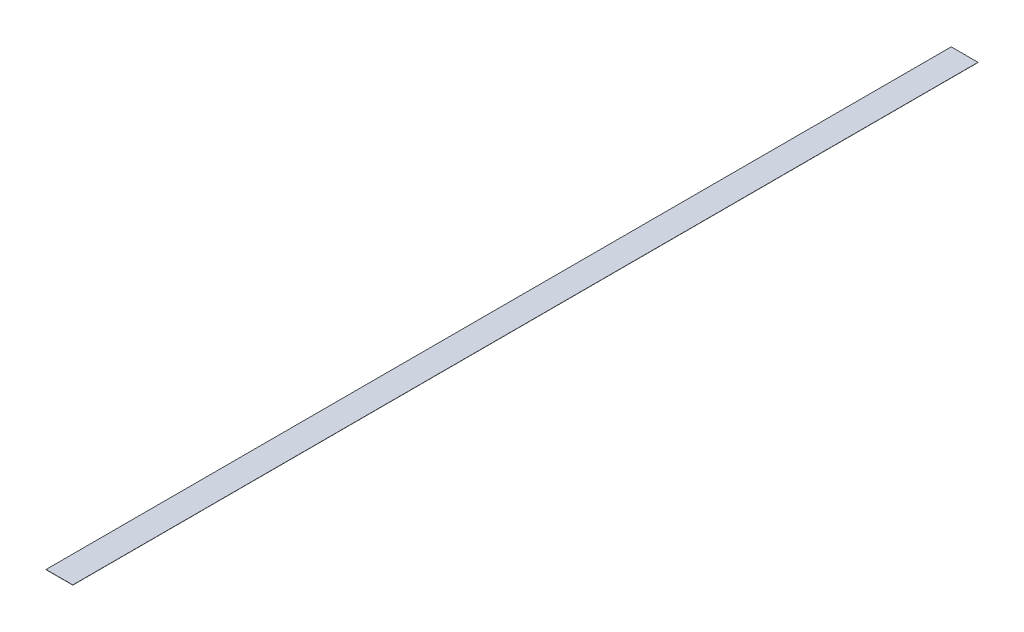
SolidWorks part; units mm, degrees
ref_plane "Front Plane" through (0, 0, 0) normal (0, 0, 1) x (1, 0, 0)
ref_plane "Top Plane" through (0, 0, 0) normal (0, 1, 0) x (1, 0, 0)
ref_plane "Right Plane" through (0, 0, 0) normal (1, 0, 0) x (0, 0, -1)
sketch "Sketch1" plane through (0, 0, 0) normal (0, 1, 0) x (1, 0, 0)
  line L5 (0, 0) -> (15, 0)
  line L6 (0, 0) -> (0, -507)
  line L7 (0, -507) -> (15, -507)
  line L8 (15, 0) -> (15, -507)
  dimension "D1" = 507
  dimension "D2" = 15
extrude "Boss-Extrude1" add sketch "Sketch1" along normal blind 0.1 contours L6 L7 L8 L5
sketch "Sketch2" plane through (0, 0.1, 0) normal (0, 1, 0) x (1, 0, 0)
  line L0 (0, -487) -> (15, -483.537) construction
  line L1 (0, 0) -> (0, -507) construction
  line L2 (15, 0) -> (15, -507) construction
  line L3 (5.0641, -485.8309) -> (5.0641, -457.2309) construction
  circle A0 centre (5.0641, -485.8309) radius 1
  circle A1 centre (9.9359, -484.7061) radius 1
  circle A2 centre (5.0641, -457.2309) radius 1
  circle A3 centre (9.9359, -456.1061) radius 1
  circle A4 centre (5.0641, -428.6309) radius 1
  circle A5 centre (9.9359, -427.5061) radius 1
  circle A6 centre (5.0641, -400.0309) radius 1
  circle A7 centre (9.9359, -398.9061) radius 1
  circle A8 centre (5.0641, -371.4309) radius 1
  circle A9 centre (9.9359, -370.3061) radius 1
  circle A10 centre (5.0641, -342.8309) radius 1
  circle A11 centre (9.9359, -341.7061) radius 1
  circle A12 centre (5.0641, -314.2309) radius 1
  circle A13 centre (9.9359, -313.1061) radius 1
  circle A14 centre (5.0641, -285.6309) radius 1
  circle A15 centre (9.9359, -284.5061) radius 1
  circle A16 centre (5.0641, -257.0309) radius 1
  circle A17 centre (9.9359, -255.9061) radius 1
  circle A18 centre (5.0641, -228.4309) radius 1
  circle A19 centre (9.9359, -227.3061) radius 1
  circle A20 centre (5.0641, -199.8309) radius 1
  circle A21 centre (9.9359, -198.7061) radius 1
  circle A22 centre (5.0641, -171.2309) radius 1
  circle A23 centre (9.9359, -170.1061) radius 1
  circle A24 centre (5.0641, -142.6309) radius 1
  circle A25 centre (9.9359, -141.5061) radius 1
  circle A26 centre (5.0641, -114.0309) radius 1
  circle A27 centre (9.9359, -112.9061) radius 1
  circle A28 centre (5.0641, -85.4309) radius 1
  circle A29 centre (9.9359, -84.3061) radius 1
  circle A30 centre (5.0641, -56.8309) radius 1
  circle A31 centre (9.9359, -55.7061) radius 1
  point P13 (7.5, -485.2685)
  dimension "D3" = 2
  dimension "D4" = 5
  dimension "D1" = 20
  dimension "D2" = 77
  dimension "D5" = 2.5
  dimension "D7" = 28.6
  dimension "D6" = 16
extrude "Cut-Extrude1" [suppressed] cut sketch "Sketch2" against normal through all
